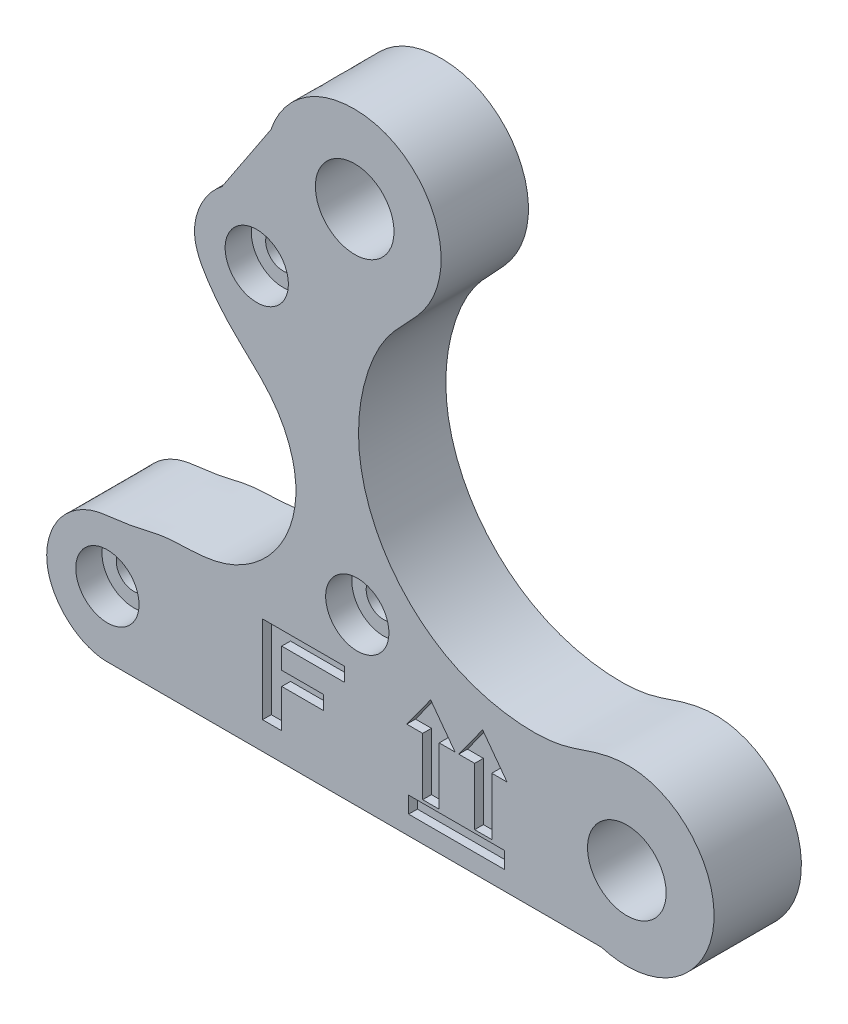
SolidWorks part; units mm, degrees
ref_plane "Piano frontale" through (0, 0, 0) normal (0, 0, 1) x (1, 0, 0)
ref_plane "Piano superiore" through (0, 0, 0) normal (0, 1, 0) x (1, 0, 0)
ref_plane "Piano destro" through (0, 0, 0) normal (1, 0, 0) x (0, 0, -1)
sketch "Model" plane through (0, 0, 0) normal (0, 0, 1) x (1, 0, 0)
  line L0 (23.8221, -29.1574) -> (-32.3603, -29.1521)
  line L1 (-14.0392, 33.0001) -> (-19.6464, 24.5403)
  line L3 (-12.8, -26) -> (-12.8, -21.6)
  line L4 (-12.8, -21.6) -> (-8, -21.6)
  line L5 (-8, -21.6) -> (-8, -20)
  line L6 (-8, -20) -> (-12.8, -20)
  line L7 (-12.8, -20) -> (-12.8, -17.6)
  line L8 (-12.8, -17.6) -> (-5.6, -17.6)
  line L9 (-5.6, -17.6) -> (-5.6, -16)
  line L10 (-5.6, -16) -> (-15, -16)
  line L11 (-15, -16) -> (-15, -26)
  line L12 (-15, -26) -> (-12.8, -26)
  line L13 (12.72, -27) -> (12.72, -25.11)
  line L14 (12.72, -25.11) -> (1.73, -25.11)
  line L15 (1.73, -25.11) -> (1.73, -27)
  line L16 (1.73, -27) -> (12.72, -27)
  line L17 (3.34, -18.18) -> (3.34, -24.76)
  line L18 (3.34, -24.76) -> (5.23, -24.76)
  line L19 (5.23, -24.76) -> (5.23, -18.18)
  line L20 (5.23, -18.18) -> (7.05, -18.18)
  line L21 (7.05, -18.18) -> (4.25, -14.4)
  line L22 (4.25, -14.4) -> (1.52, -18.18)
  line L23 (1.52, -18.18) -> (3.34, -18.18)
  line L24 (9.29, -18.18) -> (9.29, -24.76)
  line L25 (9.29, -24.76) -> (11.25, -24.76)
  line L26 (11.25, -24.76) -> (11.25, -18.18)
  line L27 (11.25, -18.18) -> (13, -18.18)
  line L28 (13, -18.18) -> (10.2, -14.4)
  line L29 (10.2, -14.4) -> (7.47, -18.18)
  line L30 (7.47, -18.18) -> (9.29, -18.18)
  circle A0 centre (-32.7642, -21.6566) radius 3.6222
  circle A1 centre (-32.7642, -21.6566) radius 1.9821
  circle A2 centre (26.7171, -20.0798) radius 4.5
  circle A3 centre (-4.4467, 29.913) radius 4.5
  circle A4 centre (-15.6609, 18.6648) radius 3.6222
  circle A5 centre (-15.6609, 18.6648) radius 1.9821
  circle A6 centre (-4.1483, -10.151) radius 3.6222
  circle A7 centre (-4.1483, -10.151) radius 1.9821
  spline S0 degree 3 poles (-19.6464, 24.5403) (-21.5648, 23.1052) (-23.8417, 18.9539) (-21.3029, 14.2555) (-18.1288, 10.3119) (-12.9958, 6.3772) (-10.3068, -1.2868) (-12.8421, -8.9196) (-18.2384, -12.7937) (-22.977, -13.3585) (-26.6542, -13.3543) (-30.4787, -14.5452) (-35.1156, -14.6512) (-39.1442, -17.9497) (-40.6651, -25.0635) (-35.8383, -29.356) (-32.3603, -29.1521) knots 0 0 0 0 0.094014 0.141298 0.188882 0.283264 0.37644 0.46967 0.562856 0.604372 0.645683 0.698737 0.75199 0.814118 0.875937 1 1 1 1
  spline S1 degree 3 poles (-14.0392, 33.0001) (-13.1907, 35.5668) (-9.4285, 39.8905) (-1.2405, 40.2272) (4.2244, 35.8491) (6.1018, 29.7859) (4.0886, 23.7048) (-0.7146, 19.8469) (-3.7543, 13.3186) (-4.532, 5.0907) (-1.0834, -3.596) (5.8331, -9.8721) (13.3226, -11.9079) (19.432, -11.6223) (23.6177, -9.821) (28.2387, -9.3172) (33.0546, -11.2521) (36.644, -15.836) (37.0826, -22.8303) (32.1096, -29.337) (26.4098, -29.9352) (23.8221, -29.1574) knots 0 0 0 0 0.062813 0.124346 0.171053 0.21776 0.264487 0.311759 0.359006 0.429474 0.499931 0.570387 0.640844 0.676292 0.711745 0.747019 0.782283 0.828982 0.875682 0.937205 1 1 1 1
extrude "Main body" add sketch "Model" against normal blind 10 contours S0 L0 S1 L1 | A5 | A3 | A2 | A7 | A1
extrude "Symbols" cut sketch "Model<5>" against normal blind 1 contours L11 L12 L3 L4 L5 L6 L7 L8 L9 L10 | L22 L23 L17 L18 L19 L20 L21 | L15 L16 L13 L14 | L29 L30 L24 L25 L26 L27 L28 region at (-13.9, -25.8628, 0) region at (7.225, -26.055, 0) region at (4.2797, -19.3923, 0) region at (10.2491, -19.4332, 0)
sketch "Model<5>" plane through (0, 0, 0) normal (0, 0, 1) x (1, 0, 0) same geometry as "Model"
extrude "Recess holes" cut sketch "Model<6>" against normal blind 3 contours A4 A5 | A0 A1 | A6 A7 region at (-36.2839, -21.6566, 0) region at (-19.1807, 18.6648, 0) region at (-7.668, -10.151, 0)
sketch "Model<6>" plane through (0, 0, 0) normal (0, 0, 1) x (1, 0, 0) same geometry as "Model"
ref_axis "Rod1 axis" through (-4.4467, 29.913, -10) along (0, 0, 1)
ref_axis "Rod2 axis" through (26.7171, -20.0798, -10) along (0, 0, 1)
ref_axis "Motor screw 1" through (-32.7642, -21.6566, -10) along (0, 0, 1)
ref_axis "Motor screw 2" through (-4.1483, -10.151, -10) along (0, 0, 1)
ref_axis "Motor screw 3" through (-15.6609, 18.6648, -10) along (0, 0, 1)
